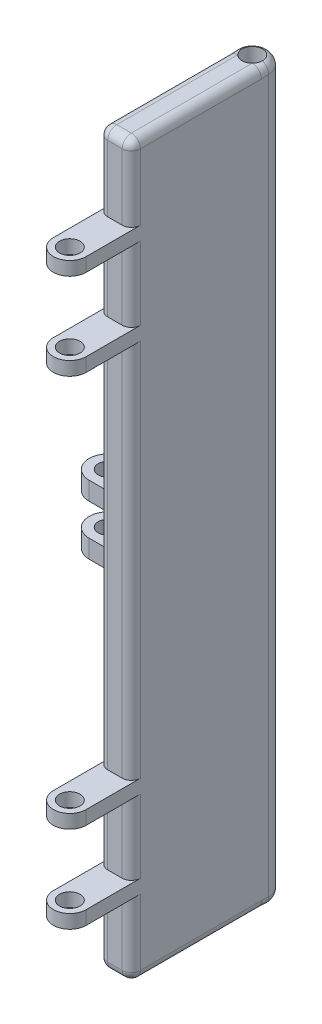
SolidWorks part; units mm, degrees
ref_plane "Front Plane" through (0, 0, 0) normal (0, 0, 1) x (1, 0, 0)
ref_plane "Top Plane" through (0, 0, 0) normal (0, 1, 0) x (1, 0, 0)
ref_plane "Right Plane" through (0, 0, 0) normal (1, 0, 0) x (0, 0, -1)
sketch "Sketch1" plane through (0, 0, 0) normal (0, 1, 0) x (1, 0, 0)
  line L0 (0, 0) -> (0, -40) construction
  line L1 (3.6, 0) -> (3.6, -40)
  line L2 (-3.6, 0) -> (-3.6, -40)
  arc A0 (3.6, 0) -> (-3.6, 0) centre (0, 0) ccw
  arc A1 (-3.6, -40) -> (3.6, -40) centre (0, -40) ccw
  circle A2 centre (0, 0) radius 2.25
  circle A3 centre (0, -40) radius 2.25
  point P3 (0, -20)
  dimension "D1" = 4.5
  dimension "D2" = 3.6
  dimension "D3" = 40
extrude "Boss-Extrude1" add sketch "Sketch1" along normal blind 160
sketch "Sketch2" plane through (3.6, 0, 0) normal (1, 0, 0) x (0, 0, -1)
  line L0 (-43.6, 160) -> (-43.6, 0) construction
  line L1 (-30.1, 140.5) -> (-43.6, 140.5)
  line L2 (-30.1, 140.5) -> (-30.1, 124.5)
  line L3 (-30.1, 124.5) -> (-43.6, 124.5)
  line L4 (-43.6, 140.5) -> (-43.6, 124.5)
  line L5 (3.6, 80) -> (-43.6, 80) construction
  line L6 (3.6, 0) -> (3.6, 160) construction
  line L7 (-43.6, 19.5) -> (-43.6, 35.5)
  line L8 (-30.1, 35.5) -> (-43.6, 35.5)
  line L9 (-30.1, 19.5) -> (-30.1, 35.5)
  line L10 (-30.1, 19.5) -> (-43.6, 19.5)
  line L11 (-40, 160) -> (0, 160) construction
  line L12 (-30.1, 160) -> (-43.6, 160)
  line L13 (-30.1, 160) -> (-30.1, 143.5)
  line L14 (-30.1, 143.5) -> (-43.6, 143.5)
  line L15 (-43.6, 160) -> (-43.6, 143.5)
  line L16 (-43.6, 160) -> (-43.6, 0) construction
  line L17 (-30.1, 16.5) -> (-43.6, 16.5)
  line L18 (-43.6, 0) -> (-43.6, 16.5)
  line L19 (-30.1, 0) -> (-43.6, 0)
  line L20 (-30.1, 0) -> (-30.1, 16.5)
  line L22 (-43.6, 121.5) -> (-30.1, 121.5)
  line L23 (-43.6, 121.5) -> (-43.6, 38.5)
  line L24 (-43.6, 38.5) -> (-30.1, 38.5)
  line L25 (-30.1, 121.5) -> (-30.1, 38.5)
  point P26 (-30.1, 80)
  dimension "D1" = 16
  dimension "D2" = 121
  dimension "D3" = 3
  dimension "13.5" = 13.5
  dimension "D5" = 3
extrude "Cut-Extrude1" cut sketch "Sketch2" against normal through all
fillet "Fillet1" radius 2 16 edges at (-3.6, 160, 15.05) (3.6, 160, 15.05) (0, 160, 30.1) (-3.6, 0, 15.05) (0, 0, 30.1) (3.6, 0, 15.05) (-3.6, 8.25, 30.1) (3.6, 8.25, 30.1) (3.6, 27.5, 30.1) (-3.6, 27.5, 30.1) (3.6, 132.5, 30.1) (-3.6, 80, 30.1) (3.6, 80, 30.1) (3.6, 151.75, 30.1) (-3.6, 151.75, 30.1) (-3.6, 132.5, 30.1)
ref_plane "Plane1" through (0, 80, 0) normal (0, 1, 0) x (1, 0, 0)
sketch "Sketch4" plane through (0, 80, 0) normal (0, 1, 0) x (1, 0, 0)
  line L0 (3.6, -17.85) -> (3.6, -26.15) construction
  line L1 (3.6, -1.5819) -> (3.6, -28.1) construction
  line L2 (3.6, -17.85) -> (9.6, -17.85) construction
  line L3 (3.6, -26.15) -> (9.6, -26.15) construction
  line L4 (0, 0) -> (0, -28.1) construction
  line L5 (-1.6, -28.1) -> (1.6, -28.1) construction
  line L6 (-3.6, -26.15) -> (-9.6, -26.15)
  line L7 (-3.6, -17.85) -> (-9.6, -17.85)
  line L8 (-3.6, -17.85) -> (-3.6, -26.15)
  circle A0 centre (9.6, -22) radius 2.15 construction
  arc A1 (9.6, -26.15) -> (9.6, -17.85) centre (9.6, -22) ccw construction
  arc A2 (-9.6, -26.15) -> (-9.6, -17.85) centre (-9.6, -22) cw
  circle A3 centre (-9.6, -22) radius 2.15
  dimension "D1" = 4.3
  dimension "D2" = 6
  dimension "D4" = 2
  dimension "D3" = 22
extrude "Boss-Extrude2" add sketch "Sketch4" along normal mid plane 15
sketch "Sketch5" plane through (0, 0, 17.85) normal (0, 0, -1) x (-1, 0, 0)
  line L8 (3.6, 87.5) -> (3.6, 72.5) construction
  line L9 (3.6, 83.5) -> (13.75, 83.5)
  line L10 (3.6, 83.5) -> (3.6, 76.5)
  line L11 (3.6, 76.5) -> (13.75, 76.5)
  line L12 (13.75, 83.5) -> (13.75, 76.5)
  line L13 (13.75, 72.5) -> (13.75, 87.5) construction
  line L14 (9.6, 87.5) -> (9.6, 72.5) construction
  point P6 (10.4133, 72.3943)
  point P14 (9.6, 80)
  point P16 (13.75, 80)
  dimension "D1" = 4
extrude "Cut-Extrude2" cut sketch "Sketch5" against normal blind 15
